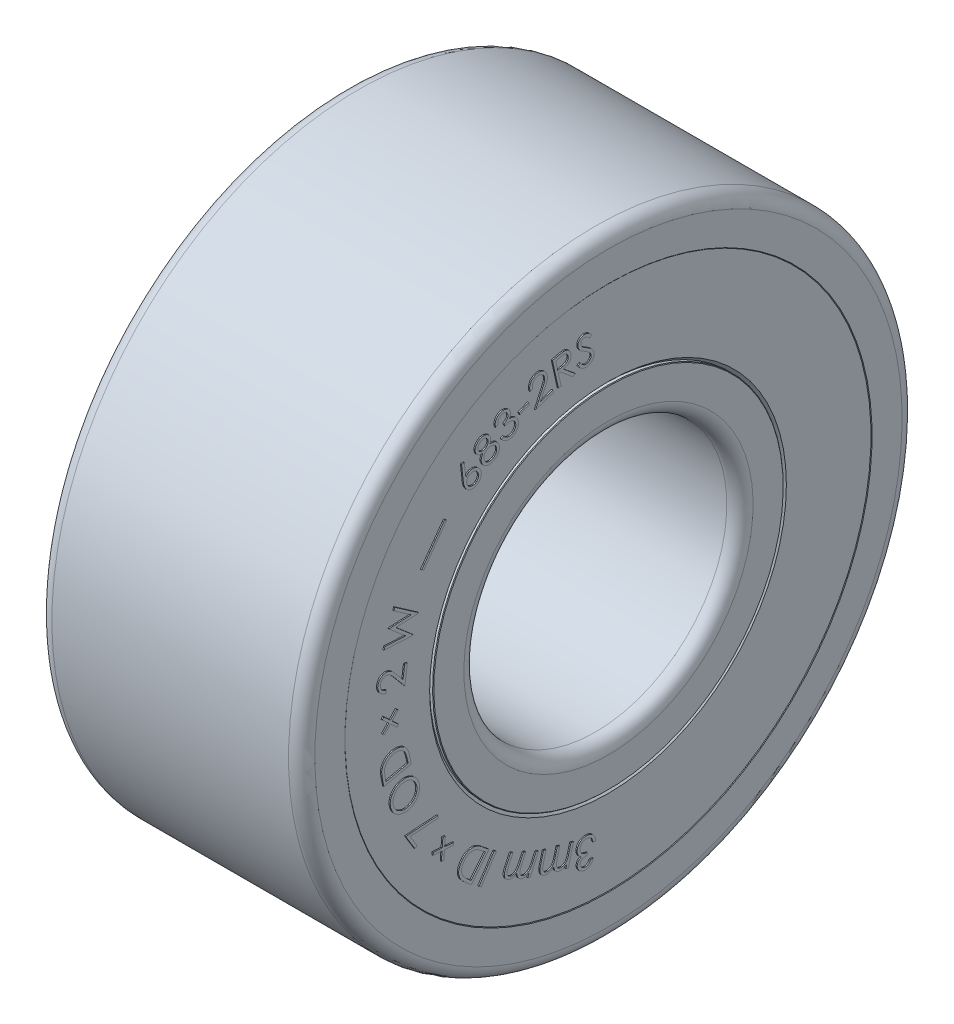
SolidWorks part; units mm, degrees
material "AISI 316 Annealed Stainless Steel Bar (SS)"
ref_plane "Front" through (0, 0, 0) normal (0, 0, 1) x (1, 0, 0)
ref_plane "Top" through (0, 0, 0) normal (0, 1, 0) x (1, 0, 0)
ref_plane "Right" through (0, 0, 0) normal (1, 0, 0) x (0, 0, -1)
sketch "LAYOUT R" plane through (0, 0, 0) normal (1, 0, 0) x (0, 0, -1)
  line L0 (-1.5, 1.5) -> (1.5, 1.5)
  line L1 (1.5, -3.5) -> (-1.5, -3.5) construction
  line L2 (1.5, -3.5) -> (1.5, 3.5) construction
  line L3 (1.5, 3.5) -> (-1.5, 3.5)
  line L4 (-1.5, -3.5) -> (-1.5, 3.5) construction
  line L5 (1.5, -3.5) -> (-1.5, 3.5) construction
  line L6 (1.5, 3.5) -> (-1.5, -3.5) construction
  line L7 (-1.5, 2) -> (1.5, 2)
  line L8 (-1.5, 3) -> (1.5, 3)
  line L11 (-3.81, 0) -> (3.81, 0) construction
  line L12 (-1.5, 3.5) -> (-1.5, 3)
  line L13 (1.5, 3.5) -> (1.5, 3)
  line L14 (-1.5, 3) -> (-1.5, 2)
  line L15 (1.5, 3) -> (1.5, 2)
  line L16 (-1.5, 2) -> (-1.5, 1.5)
  line L17 (1.5, 2) -> (1.5, 1.5)
  line L18 (-1.4945, 3) -> (-1.4945, 2)
  line L19 (1.4945, 3) -> (1.4945, 2)
  point P0 (0, 0)
  point P15 (0, 0)
  dimension "D1" = 3
  dimension "D2" = 7
  dimension "D3" = 1.5
  dimension "D6" = 0.0055
  dimension "D7" = 0.0055
  dimension "D4" = 2
  dimension "D5" = 3
sketch "Sketch R, INNER BODY" plane through (0, 0, 0) normal (1, 0, 0) x (0, 0, -1)
  line L0 (-1.5, 1.5) -> (1.5, 1.5) construction
  line L2 (-1.5, 2) -> (1.5, 2) construction
  line L4 (-1.5, 1.5) -> (1.5, 1.5)
  line L6 (-1.5, 2) -> (1.5, 2)
  line L8 (1.5, 2) -> (1.5, 1.5) construction
  line L9 (-1.5, 2) -> (-1.5, 1.5) construction
  line L10 (1.5, 2) -> (1.5, 1.5)
  line L11 (-1.5, 2) -> (-1.5, 1.5)
  line L12 (-3.81, 0) -> (3.81, 0) construction
  line L13 (-3.81, 0) -> (3.81, 0) construction
sketch "Sketch R, OUTER BODY" plane through (0, 0, 0) normal (1, 0, 0) x (0, 0, -1)
  line L0 (-1.5, 3) -> (1.5, 3) construction
  line L1 (1.5, 3.5) -> (1.5, 3) construction
  line L8 (-3.81, 0) -> (3.81, 0) construction
  line L9 (-3.81, 0) -> (3.81, 0) construction
  line L16 (1.5, 3.5) -> (-1.5, 3.5) construction
  line L17 (-1.5, 3.5) -> (-1.5, 3) construction
  line L18 (-1.5, 3) -> (1.5, 3)
  line L19 (1.5, 3.5) -> (1.5, 3)
  line L22 (1.5, 3.5) -> (-1.5, 3.5)
  line L23 (-1.5, 3.5) -> (-1.5, 3)
sketch "Sketch R, SEAL FACES" plane through (0, 0, 0) normal (1, 0, 0) x (0, 0, -1)
  line L0 (-3.81, 0) -> (3.81, 0) construction
  line L1 (-3.81, 0) -> (3.81, 0) construction
  line L3 (-1.5, 2) -> (1.5, 2) construction
  line L5 (-1.5, 3) -> (1.5, 3) construction
  line L7 (-1.4945, 2) -> (1.4945, 2)
  line L9 (-1.4945, 3) -> (1.4945, 3)
  line L10 (1.4945, 3) -> (1.4945, 2) construction
  line L11 (-1.4945, 3) -> (-1.4945, 2) construction
  line L12 (1.4945, 3) -> (1.4945, 2)
  line L13 (-1.4945, 3) -> (-1.4945, 2)
revolve "Revolve INNER BODY" add sketch "Sketch R, INNER BODY" angle 360 about L13
fillet "Fillet INNER BODY" radius 0.15 2 edges at (0, -1.5, 1.5) (0, -1.5, -1.5)
chamfer "Chamfer INNER BODY" distance 0.007 angle 45 2 edges at (0, -2, -1.5) (0, -2, 1.5)
revolve "Revolve OUTER BODY" add sketch "Sketch R, OUTER BODY" angle 360 about L9
fillet "Fillet OUTER BODY" radius 0.15 2 edges at (0, -3.5, 1.5) (0, -3.5, -1.5)
chamfer "Chamfer OUTER BODY" distance 0.007 angle 45 2 edges at (0, -3, 1.5) (0, -3, -1.5)
revolve "Revolve SEALS" add sketch "Sketch R, SEAL FACES" angle 360 about L1
chamfer "Chamfer SEALS" distance 0.035 angle 45 2 edges at (0, -2, -1.4945) (0, -2, 1.4945)
sketch "Sketch TEXT RADIUS 1 — MANUALLY ASSIGN TEXT AND FONT SIZE (FROM EQUATIONS)" plane through (0, 0, 1.4945) normal (0, 0, 1) x (1, 0, 0)
  circle A0 centre (0, 0) radius 2.34 construction
  text T0 "3mm ID × 7 OD × 2 W  —  683-2RS" font "Century Gothic" height 0.32
  dimension "D1" = 4.68
extrude "Boss-Extrude SEAL LABEL 1" add sketch "Sketch TEXT RADIUS 1 — MANUALLY ASSIGN TEXT AND FONT SIZE (FROM EQUATIONS)" along normal blind 0.013
sketch "Sketch TEXT RADIUS 2 — MANUALLY ASSIGN TEXT AND FONT SIZE (FROM EQUATIONS)" plane through (0, 0, -1.4945) normal (0, 0, -1) x (-1, 0, 0)
  circle A0 centre (0, 0) radius 2.34 construction
  text T0 "3mm ID × 7 OD × 2 W  —  683-2RS" font "Century Gothic" height 0.32
  dimension "D1" = 4.68
extrude "Boss-Extrude SEAL LABEL 2" add sketch "Sketch TEXT RADIUS 2 — MANUALLY ASSIGN TEXT AND FONT SIZE (FROM EQUATIONS)" along normal blind 0.013
move or copy body "Body-Move/Copy1" bodies to move or copy 147 copy no rotation origin (0, 0, 0) rotation axis (0, 1, 0) rotation angle 90
equation "\"_i__BORE\"= 3"
equation "\"_i__OUTSIDE_DIAMETER\"= 7"
equation "\"_i__WIDTH\"= 3"
equation "\"_user_applied_FONT_SIZE\"= int ( \"BODY_SPAN__SEAL__OF_RADIUS\" * \"g_param__FONT_SIZE_RATIO\" * 100 ) / 100'MANUALLY ASSIGN TO FONT"
equation "\"BODY__HALF_WIDTH\"= \"_i__WIDTH\" / 2"
equation "\"BODY_SPAN___OF_DIAMETER\"= \"_i__OUTSIDE_DIAMETER\" - \"_i__BORE\""
equation "\"BODY_SPAN___OF_RADIUS\"= \"BODY_SPAN___OF_DIAMETER\" / 2"
equation "\"BODY_SPAN__BORE_AND_OD__OF RADIUS\"= ( \"BODY_SPAN___OF_RADIUS\" - \"BODY_SPAN__SEAL__OF_RADIUS\" ) / 2"
equation "\"BODY_SPAN__SEAL__OF_RADIUS\"= \"BODY_SPAN___OF_RADIUS\" * \"g_param__SEAL_PANEL_SPAN__RATIO_OF_BODY_RADIAN\""
equation "\"BORE__RADIUS\"= \"_i__BORE\" / 2"
equation "\"CORNER_RADII\"= \"_i__WIDTH\" * \"g_param__CORNER_RADII__RATIO_TO_WIDTH\""
equation "\"RING_INNER__OUTSIDE_RADIUS\"= \"BORE__RADIUS\" + \"BODY_SPAN__BORE_AND_OD__OF RADIUS\""
equation "\"RING_OUTER__OUTSIDE_RADIUS\"= ( \"_i__OUTSIDE_DIAMETER\" / 2 ) - \"BODY_SPAN__BORE_AND_OD__OF RADIUS\""
equation "\"SEAL_CHAMFERS\"= \"_i__OUTSIDE_DIAMETER\" * \"g_param__SEAL_CHAMFERS__RATIO_TO_OD\""
equation "\"SEAL_FACE_INSET\"= \"SIDE_FACE_CHAMFERS\""
equation "\"SIDE_FACE_CHAMFERS\"= \"_i__OUTSIDE_DIAMETER\" * \"g_param__SIDE_CHAMFERS__RATIO_TO_OD\""
equation "\"TEXT_RADIUS\"= \"_i__BORE\" + ( \"BODY_SPAN___OF_DIAMETER\" / 2 ) - \"_user_applied_FONT_SIZE\""
equation "\"D1@Boss-Extrude SEAL LABEL 1\" = \"g_param__INDICIA__EXTRUSION_HEIGHT\""
equation "\"D1@Boss-Extrude SEAL LABEL 2\" = \"g_param__INDICIA__EXTRUSION_HEIGHT\""
equation "\"D1@Chamfer INNER BODY\"=\"SIDE_FACE_CHAMFERS\""
equation "\"D1@Chamfer OUTER BODY\"=\"SIDE_FACE_CHAMFERS\""
equation "\"D1@Chamfer SEALS\"=\"SEAL_CHAMFERS\""
equation "\"D1@Fillet INNER BODY\"=\"CORNER_RADII\""
equation "\"D1@Fillet OUTER BODY\"=\"CORNER_RADII\""
equation "\"D1@LAYOUT R\"=\"_i__WIDTH\""
equation "\"D1@Sketch TEXT RADIUS 1 — MANUALLY ASSIGN TEXT AND FONT SIZE (FROM EQUATIONS)\" = \"TEXT_RADIUS\""
equation "\"D1@Sketch TEXT RADIUS 2 — MANUALLY ASSIGN TEXT AND FONT SIZE (FROM EQUATIONS)\" = \"TEXT_RADIUS\""
equation "\"D2@LAYOUT R\"=\"_i__OUTSIDE_DIAMETER\""
equation "\"D3@LAYOUT R\"=\"BORE__RADIUS\""
equation "\"D4@LAYOUT R\"=\"RING_INNER__OUTSIDE_RADIUS\""
equation "\"D5@LAYOUT R\"=\"RING_OUTER__OUTSIDE_RADIUS\""
equation "\"g_param__CORNER_RADII__RATIO_TO_WIDTH\"= 0.05'ISO MAX IS 0.07 WHERE WIDTH IS LESS THAN DIAMETER"
equation "\"g_param__FONT_SIZE_RATIO\"= 0.32'EXPRESSES RADIAL PROPORTION OF SEAL FACE"
equation "\"g_param__INDICIA__EXTRUSION_HEIGHT\"=0.013'RAISED INDICIA ON SEAL FACES"
equation "\"g_param__SEAL_CHAMFERS__RATIO_TO_OD\"= 0.005"
equation "\"g_param__SEAL_PANEL_SPAN__RATIO_OF_BODY_RADIAN\"= 0.5'ISO-UNSPECIFIED"
equation "\"g_param__SIDE_CHAMFERS__RATIO_TO_OD\"= 0.001'NOT ISO-SPECIFIED"
